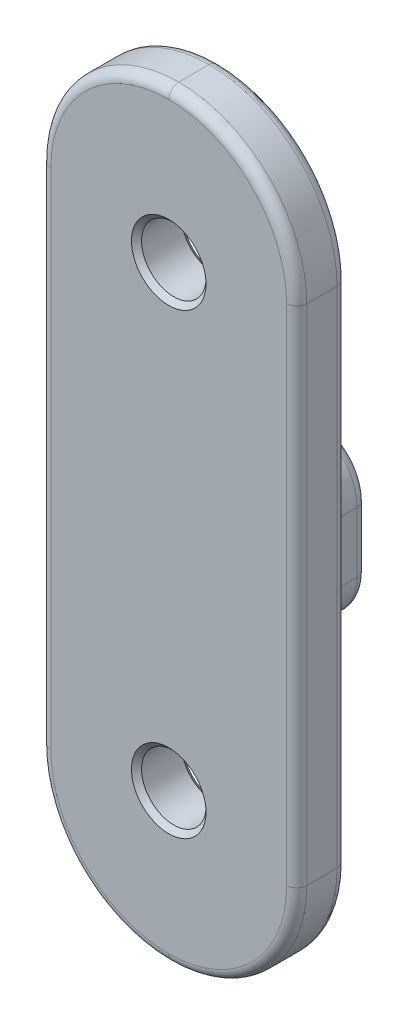
SolidWorks part; units mm, degrees
ref_plane "Front" through (0, 0, 0) normal (0, 0, 1) x (1, 0, 0)
ref_plane "Top" through (0, 0, 0) normal (0, 1, 0) x (1, 0, 0)
ref_plane "Right" through (0, 0, 0) normal (1, 0, 0) x (0, 0, -1)
sketch "Sketch1" plane through (0, 0, 0) normal (0, 0, 1) x (1, 0, 0)
  line L0 (0, 45.4) -> (0, 0) construction
  line L1 (0, 60.4) -> (0, -15) construction
  line L2 (-12.7, 60.4) -> (12.7, 60.4)
  line L3 (-12.7, 60.4) -> (-12.7, -15)
  line L4 (-12.7, -15) -> (12.7, -15)
  line L5 (12.7, 60.4) -> (12.7, -15)
  circle A0 centre (0, 0) radius 3.2
  circle A1 centre (0, 45.4) radius 3.2
  circle A3 centre (0, 45.4) radius 3.2 construction
  circle A5 centre (0, 0) radius 3.2 construction
  dimension "D1" = 6.4
  dimension "D2" = 6.4
  dimension "D5" = 25.4
  dimension "D3" = 45.4
  dimension "D4" = 15
  dimension "D6" = 15
extrude "mainBody" add sketch "Sketch1" along normal blind 5
sketch "Sketch2" plane through (0, 0, 0) normal (0, 0, -1) x (-1, 0, 0)
  line L6 (-12.7, -119.0095) -> (-12.7, 2.7) construction
  line L7 (10.9154, 12.7) -> (9.8493, 12.7) construction
  line L8 (-2.7, 12.7) -> (9.8493, 12.7) construction
  line L9 (8.7602, 32.7) -> (10.3828, 32.7) construction
  line L10 (8.7602, 32.7) -> (-2.7, 32.7) construction
  line L11 (-12.7, 42.7) -> (-12.7, 115.9656) construction
  line L12 (-12.7, -15) -> (-12.7, 60.4) construction
  line L13 (-10.7, 30.7) -> (10.7, 30.7)
  line L14 (-10.7, 30.7) -> (-10.7, 14.7)
  line L15 (-10.7, 14.7) -> (10.7, 14.7)
  line L16 (10.7, 30.7) -> (10.7, 14.7)
  line L17 (12.7, 60.4) -> (12.7, -15) construction
  arc A2 (-2.7, 12.7) -> (-12.7, 2.7) centre (-2.7, 2.7) ccw construction
  arc A3 (-12.7, 42.7) -> (-2.7, 32.7) centre (-2.7, 42.7) ccw construction
  spline S2 degree 3 poles (10.9154, 12.7) (11.3253, 12.7) (11.7124, 12.7475) (12.4403, 12.9461) (12.7577, 13.0912) (13.1717, 13.3645) (13.2975, 13.4639) (13.525, 13.6729) (13.6274, 13.7832) (13.9065, 14.1286) (14.0554, 14.3799) (14.2909, 14.8936) (14.3793, 15.158) (14.5143, 15.6974) (14.5607, 15.9732) (14.6199, 16.5277) (14.6327, 16.8062) (14.6308, 17.2246) (14.6266, 17.3642) (14.6113, 17.6436) (14.6001, 17.7841) (14.5857, 17.9229) knots 0 0 0 0 0.125 0.125 0.25 0.25 0.3125 0.3125 0.375 0.375 0.5 0.5 0.625 0.625 0.75 0.75 0.875 0.875 0.9375 0.9375 1 1 1 1 construction
  spline S3 degree 3 poles (14.0881, 27.9707) (14.091, 28.496) (14.0469, 29.0224) (13.8947, 29.7843) (13.8293, 30.0343) (13.6613, 30.5236) (13.5583, 30.7638) (13.3022, 31.2255) (13.151, 31.4441) (12.877, 31.7473) (12.7778, 31.8442) (12.56, 32.0281) (12.4413, 32.1151) (12.1879, 32.2726) (12.0526, 32.3438) (11.7623, 32.4692) (11.6061, 32.5238) (11.1125, 32.6558) (10.7601, 32.7) (10.3828, 32.7) knots 0 0 0 0 0.25 0.25 0.375 0.375 0.5 0.5 0.625 0.625 0.6875 0.6875 0.75 0.75 0.8125 0.8125 0.875 0.875 1 1 1 1 construction
  point P22 (12.7, 22.7)
  dimension "D1" = 2
  dimension "D2" = 2
  dimension "D3" = 2
  dimension "D4" = 2
extrude "ribSupport" add sketch "Sketch2" along normal blind 4
fillet "Fillet-12.7" radius 12.7 4 edges at (-12.7, -15, 2.5) (12.7, -15, 2.5) (-12.7, 60.4, 2.5) (12.7, 60.4, 2.5)
fillet "Fillet-5.0" radius 5 4 edges at (-10.7, 30.7, -2) (-10.7, 14.7, -2) (10.7, 14.7, -2) (10.7, 30.7, -2)
chamfer "Chamfer-0.5" distance 0.5 angle 45 4 edges at (3.2, 0, 0) (3.2, 0, 5) (3.2, 45.4, 0) (3.2, 45.4, 5)
fillet "Fillet-1.0" radius 1 28 edges at (9.2355, 29.2355, -4) (0, 30.7, -4) (-9.2355, 29.2355, -4) (-10.7, 22.7, -4) (-9.2355, 16.1645, -4) (0, 14.7, -4) (9.2355, 16.1645, -4) (9.2355, 29.2355, 0) (0, 30.7, 0) (-9.2355, 29.2355, 0) (-10.7, 22.7, 0) (-9.2355, 16.1645, 0) (0, 14.7, 0) (9.2355, 16.1645, 0) (8.9803, -11.2803, 0) (-8.9803, -11.2803, 0) (-12.7, 22.7, 0) (-8.9803, 56.6803, 0) (8.9803, 56.6803, 0) (8.9803, -11.2803, 5) (-8.9803, -11.2803, 5) (-12.7, 22.7, 5) (-8.9803, 56.6803, 5) (8.9803, 56.6803, 5) (10.7, 22.7, -4) (10.7, 22.7, 0) (12.7, 22.7, 0) (12.7, 22.7, 5)
equation "\"M6boltHole\"= 6.4"
equation "\"D1@Sketch1\"=\"M6boltHole\""
equation "\"D2@Sketch1\"=\"M6boltHole\""
